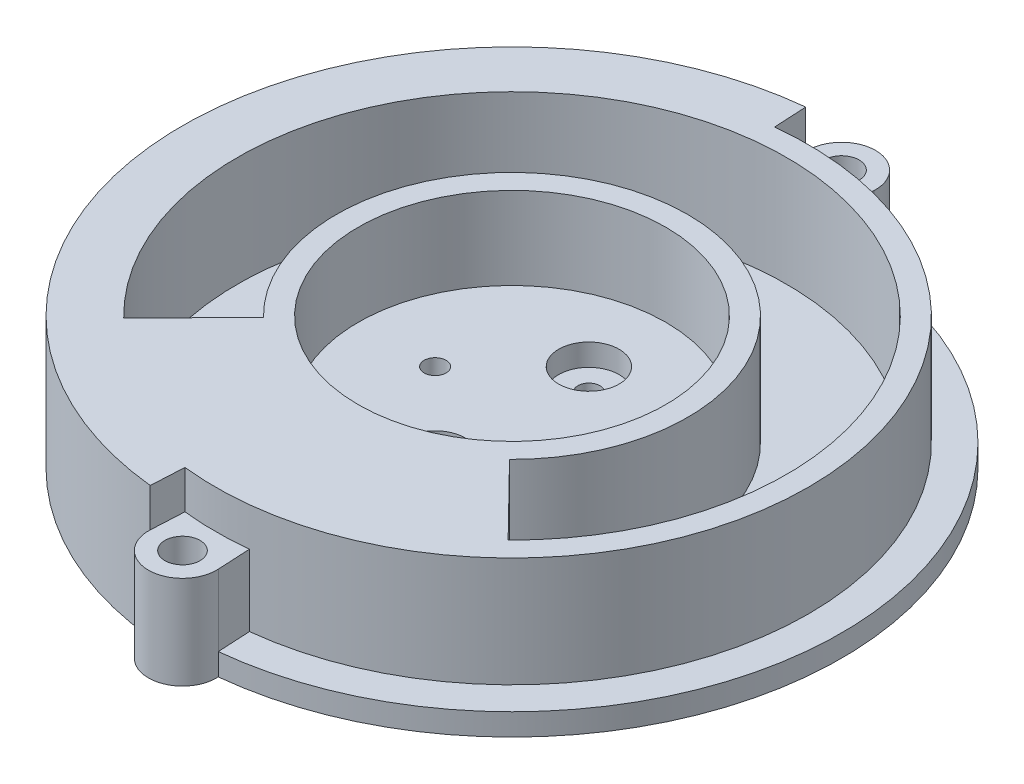
SolidWorks part; units mm, degrees
ref_plane "Front Plane" through (0, 0, 0) normal (0, 0, 1) x (1, 0, 0)
ref_plane "Top Plane" through (0, 0, 0) normal (0, 1, 0) x (1, 0, 0)
ref_plane "Right Plane" through (0, 0, 0) normal (1, 0, 0) x (0, 0, -1)
sketch "Sketch1" plane through (0, 0, 0) normal (0, 1, 0) x (1, 0, 0)
  line L0 (-17.5, -17.8536) -> (-11.2, -11.4263)
  line L1 (0, -55) -> (0, 55) construction
  line L2 (17.5, -17.8536) -> (11.2, -11.4263)
  line L4 (-17.5, -17.8536) -> (3.8221, -38.7535) construction
  circle A0 centre (0, 0) radius 27
  arc A1 (11.2, -11.4263) -> (-11.2, -11.4263) centre (0, 0) ccw
  arc A2 (17.5, -17.8536) -> (-17.5, -17.8536) centre (0, 0) ccw
  circle A3 centre (0, 0) radius 14
  arc A4 (16.5039, 11.7639) -> (14.35, -14.6399) centre (0.1913, -0.1952) cw construction
  circle A5 centre (0, 0) radius 19.9533 construction
  dimension "D1" = 54
  dimension "D2" = 2
  dimension "D3" = 9
  dimension "D4" = 2
  dimension "D5" = 35
extrude "Boss-Extrude1" add sketch "Sketch1" along normal blind 10
sketch "Sketch2" plane through (0, 0, 0) normal (0, -1, 0) x (1, 0, 0)
  circle A0 centre (0, 0) radius 30
  circle A1 centre (0, 0) radius 14 construction
  circle A2 centre (0, 0) radius 14 construction
  dimension "D1" = 60
extrude "Boss-Extrude2" add sketch "Sketch2" along normal blind 2
sketch "Sketch3" plane through (0, 0, 0) normal (0, 1, 0) x (1, 0, 0)
  line L0 (0, -13.5729) -> (0, 13.5729) construction
  line L1 (-2.5, 29.8) -> (2.5, 29.8)
  line L2 (-2.5, 29.8) -> (-2.5, 25.4032)
  line L3 (-2.5, 25.4032) -> (2.5, 25.4032)
  line L4 (2.5, 29.8) -> (2.5, 25.4032)
  line L5 (-2.5, 29.8) -> (2.5, 25.4032) construction
  line L6 (-2.5, 25.4032) -> (2.5, 29.8) construction
  line L7 (29.8, 2.5) -> (25.4032, 2.5)
  line L8 (29.8, 2.5) -> (29.8, -2.5)
  line L9 (29.8, -2.5) -> (25.4032, -2.5)
  line L10 (25.4032, 2.5) -> (25.4032, -2.5)
  line L11 (2.5, -29.8) -> (2.5, -25.4032)
  line L12 (2.5, -29.8) -> (-2.5, -29.8)
  line L13 (-2.5, -29.8) -> (-2.5, -25.4032)
  line L14 (2.5, -25.4032) -> (-2.5, -25.4032)
  line L15 (-29.8, -2.5) -> (-25.4032, -2.5)
  line L16 (-29.8, -2.5) -> (-29.8, 2.5)
  line L17 (-29.8, 2.5) -> (-25.4032, 2.5)
  line L18 (-25.4032, -2.5) -> (-25.4032, 2.5)
  circle A1 centre (0, 0) radius 27 construction
  point P0 (0, 27.6016)
  dimension "D2" = 29.8
  dimension "D1" = 5
  dimension "D3" = 4
extrude "Boss-Extrude3" [suppressed] add sketch "Sketch3" along normal blind 10
sketch "Sketch5" [suppressed] plane through (0, 0, 0) normal (0, 1, 0) x (1, 0, 0)
  line L0 (0, 29.8) -> (0, 30)
  line L1 (2.5, 29.8) -> (-2.5, 29.8) construction
  line L2 (0, -13.5729) -> (0, 13.5729) construction
  line L3 (0, -29.8) -> (0, -30)
  line L4 (0, 29.8) -> (-2.5, 29.8)
  line L5 (-2.5, 29.8) -> (-2.5, 26.884)
  line L6 (-26.884, 2.5) -> (-29.8, 2.5)
  line L7 (-29.8, 2.5) -> (-29.8, -2.5)
  line L8 (-29.8, -2.5) -> (-26.884, -2.5)
  line L9 (-2.5, -26.884) -> (-2.5, -29.8)
  line L10 (-2.5, -29.8) -> (0, -29.8)
  line L11 (-2.5, -29.8) -> (2.5, -29.8) construction
  circle A0 centre (0, 0) radius 30 construction
  arc A1 (0, 30) -> (0, -30) centre (0, 0) ccw
  arc A2 (-26.884, 2.5) -> (-2.5, 26.884) centre (0, 0) cw
  arc A3 (-26.884, -2.5) -> (-2.5, -26.884) centre (0, 0) ccw
extrude "Boss-Extrude4" [suppressed] add sketch "Sketch5" along normal up to surface (10 mm away) up to face at (0, 10, 27)
ref_plane "Plane1" through (0, 2.5, 0) normal (0, 1, 0) x (1, 0, 0)
sketch "Sketch6" plane through (0, 2.5, 0) normal (0, 1, 0) x (1, 0, 0)
  circle A0 centre (0, 0) radius 14
extrude "Boss-Extrude5" add sketch "Sketch6" against normal up to surface (2.5 mm away) up to face at (0, 0, 14)
sketch "Sketch4" plane through (0, -2, 0) normal (0, -1, 0) x (1, 0, 0)
  circle A0 centre (0, 0) radius 7 construction
  circle A1 centre (0, -7) radius 1
  circle A2 centre (-7, 0) radius 1
  circle A3 centre (0, 7) radius 1
  circle A4 centre (7, 0) radius 1
  point P14 (0, 0)
  dimension "D1" = 14
  dimension "D2" = 2
  dimension "D3" = 4
extrude "Cut-Extrude1" cut sketch "Sketch4" against normal through all both and the other way through all
sketch "Sketch7" plane through (0, 10, 0) normal (0, 1, 0) x (1, 0, 0)
  line L0 (11.2, -11.4263) -> (17.5, -17.8536) construction
  circle A0 centre (0, 0) radius 20.5 construction
  circle A1 centre (0, -20.5) radius 1.6
  point P5 (14.35, -14.6399)
  dimension "D1" = 3.2
extrude "Cut-Extrude2" [suppressed] cut sketch "Sketch7" against normal through all both and the other way through all
sketch "Sketch8" [suppressed] plane through (0, -2, 0) normal (0, -1, 0) x (1, 0, 0)
  line L0 (6.6, 0) -> (-6.6, 0) construction
  line L1 (-3.1177, 20.5) -> (-1.5588, 17.8)
  line L2 (-1.5588, 17.8) -> (1.5588, 17.8)
  line L3 (1.5588, 17.8) -> (3.1177, 20.5)
  line L4 (3.1177, 20.5) -> (1.5588, 23.2)
  line L5 (1.5588, 23.2) -> (-1.5588, 23.2)
  line L6 (-1.5588, 23.2) -> (-3.1177, 20.5)
  circle A0 centre (0, 20.5) radius 2.7 construction
  dimension "D1" = 5.4
extrude "Cut-Extrude3" [suppressed] cut sketch "Sketch8" against normal blind 4
sketch "Sketch9" [suppressed] plane through (0, 0, 0) normal (1, 0, 0) x (0, 0, -1)
  line L0 (30, 10) -> (-30, 10) construction
  line L1 (33.5, -2) -> (28, -2)
  line L3 (33.5, 10) -> (28, 10)
  line L4 (28, -2) -> (28, 10)
  line L5 (30, 10) -> (30, 0) construction
  arc A0 (33.5, -2) -> (33.5, 10) centre (33.5, 4) ccw
  circle A1 centre (33.5, 4) radius 1.6
  circle A2 centre (33.5, 4) radius 3 construction
  dimension "D4" = 3.2
  dimension "D5" = 6
  dimension "D1" = 3.5
  dimension "D2" = 2
  dimension "D3" = 12
extrude "Boss-Extrude6" [suppressed] add sketch "Sketch9" against normal blind 2
mirror "Mirror1" [suppressed] about plane through (0, 0, 0) normal (0, 0, 1)
sketch "Sketch10" plane through (0, 2.5, 0) normal (0, 1, 0) x (1, 0, 0)
  circle A0 centre (0, 7) radius 2.75
  circle A1 centre (0, -7) radius 2.75
  dimension "D1" = 5.5
  dimension "D2" = 5.5
extrude "Cut-Extrude4" cut sketch "Sketch10" against normal blind 2
sketch "Sketch11" plane through (0, -2, 0) normal (0, -1, 0) x (1, 0, 0)
  circle A0 centre (0, 0) radius 4.25
  dimension "D1" = 8.5
extrude "Cut-Extrude5" cut sketch "Sketch11" against normal blind 1
sketch "Sketch12" plane through (0, 0, 0) normal (0, 1, 0) x (1, 0, 0)
  line L1 (3.0959, 29.8398) -> (2.9406, 26.8394)
  line L4 (-6.6, 0) -> (6.6, 0) construction
  line L5 (-3.0959, 29.8398) -> (-2.9406, 26.8394) construction
  line L6 (-3.0959, -29.8398) -> (-2.9406, -26.8394)
  arc A0 (2.9406, 26.8394) -> (-2.9406, -26.8394) centre (0, 0) ccw
  circle A2 centre (0, 30) radius 1.6
  arc A4 (3.0959, 29.8398) -> (-3.0959, 29.8398) centre (0, 30) ccw
  arc A5 (-3.0959, 29.8398) -> (-3.0959, -29.8398) centre (0, 0) ccw
  circle A6 centre (0, 0) radius 27 construction
  circle A7 centre (0, 0) radius 30 construction
  circle A8 centre (0, 0) radius 27 construction
  arc A9 (3.0959, -29.8398) -> (-3.0959, -29.8398) centre (0, -30) cw construction
  point P11 (0, 0)
  point P17 (-2.9241, -26.8412)
  point P20 (0, 0)
  dimension "D1" = 3.2
  dimension "D2" = 1.5
extrude "Boss-Extrude7" add sketch "Sketch12" along normal blind 6.5
sketch "Sketch13" plane through (0, 6.5, 0) normal (0, 1, 0) x (1, 0, 0)
  line L0 (-3.0959, 29.8398) -> (-2.9406, 26.8394)
  line L3 (-2.9406, -26.8394) -> (-3.0959, -29.8398)
  circle A0 centre (0, 0) radius 27 construction
  arc A1 (3.0959, 29.8398) -> (-3.0959, 29.8398) centre (0, 30) ccw construction
  arc A2 (-2.9406, -26.8394) -> (-2.9406, 26.8394) centre (0, 0) cw
  arc A4 (-3.0959, 29.8398) -> (-3.0959, -29.8398) centre (0, 0) ccw construction
  arc A6 (-3.0959, -29.8398) -> (-3.0959, 29.8398) centre (0, 0) cw
extrude "Boss-Extrude8" add sketch "Sketch13" along normal up to surface (3.5 mm away) up to face at (0, 10, 27)
mirror "Mirror2" about plane through (0, 0, 0) normal (0, 0, 1) of "Boss-Extrude7"
sketch "Sketch14" plane through (0, -2, 0) normal (0, -1, 0) x (1, 0, 0)
  line L0 (6.6, 0) -> (-6.6, 0) construction
  circle A0 centre (0, -30) radius 3.1
  arc A1 (-3.0959, -29.8398) -> (3.0959, -29.8398) centre (0, -30) ccw construction
  circle A2 centre (0, 30) radius 3.1
extrude "Boss-Extrude9" add sketch "Sketch14" against normal up to surface (2 mm away) up to face at (0, 0, -31.129)
sketch "Sketch15" plane through (0, -2, 0) normal (0, -1, 0) x (1, 0, 0)
  line L0 (6.6, 0) -> (-6.6, 0) construction
  circle A0 centre (0, -30) radius 1.6
  circle A1 centre (0, 30) radius 1.6
  dimension "D1" = 3.2
extrude "Cut-Extrude9" cut sketch "Sketch15" against normal through all
